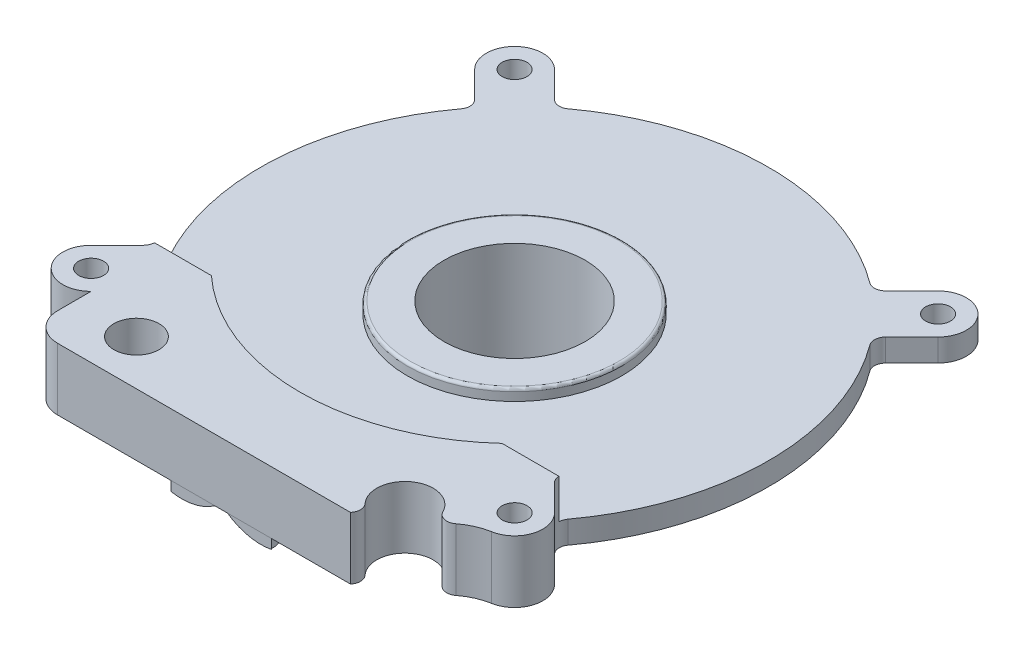
SolidWorks part; units mm, degrees
ref_plane "前视基准面" through (0, 0, 0) normal (0, 0, 1) x (1, 0, 0)
ref_plane "上视基准面" through (0, 0, 0) normal (0, 1, 0) x (1, 0, 0)
ref_plane "右视基准面" through (0, 0, 0) normal (1, 0, 0) x (0, 0, -1)
sketch "草图1" plane through (0, 0, 0) normal (0, 1, 0) x (1, 0, 0)
  circle A0 centre (0, 0) radius 12.5
  circle A1 centre (0, 0) radius 15
  dimension "D1" = 30
  dimension "D2" = 25
extrude "凸台-拉伸1" add sketch "草图1" along normal blind 20
sketch "草图2" plane through (0, 20, 0) normal (0, 1, 0) x (1, 0, 0)
  circle A0 centre (0, 0) radius 17
  circle A1 centre (0, 0) radius 12.5
  dimension "D1" = 34
  dimension "D2" = 25
extrude "凸台-拉伸2" add sketch "草图2" along normal blind 6
sketch "草图3" plane through (0, 0, 0) normal (0, -1, 0) x (1, 0, 0)
  line L0 (0, 0) -> (9.5, 0) construction
  circle A0 centre (0, 0) radius 7
  circle A2 centre (0, 0) radius 12.5
  circle A3 centre (9.5, 0) radius 1.65
  circle A4 centre (-4.75, -8.2272) radius 1.65
  circle A5 centre (-4.75, 8.2272) radius 1.65
  point P12 (0, 0)
  dimension "D1" = 14
  dimension "D2" = 25
  dimension "D3" = 3.3
  dimension "D4" = 9.5
  dimension "D5" = 3
extrude "凸台-拉伸3" add sketch "草图3" against normal blind 3
sketch "草图5" plane through (0, 26, 0) normal (0, 1, 0) x (1, 0, 0)
  line L1 (19, 19) -> (-19, 19)
  line L2 (19, 19) -> (19, -19)
  line L3 (19, -19) -> (-19, -19)
  line L4 (-19, 19) -> (-19, -19)
  line L5 (19, 19) -> (-19, -19) construction
  line L6 (19, -19) -> (-19, 19) construction
  circle A0 centre (0, 0) radius 19
  circle A1 centre (0, 0) radius 17
  point P0 (0, 0)
  circle M3 centre (0, 0) radius 17
  dimension "D3" = 34
  dimension "D1" = 38
  dimension "D2" = 38
extrude "凸台-拉伸5" add sketch "草图5" against normal blind 2 contours A0 M3
sketch "草图6" plane through (0, 26, 0) normal (0, 1, 0) x (1, 0, 0)
  line L1 (13, -13) -> (-13, -13)
  line L2 (13, -13) -> (13, 13)
  line L3 (13, 13) -> (-13, 13)
  line L4 (-13, -13) -> (-13, 13)
  line L5 (13, -13) -> (-13, 13) construction
  line L6 (13, 13) -> (-13, -13) construction
  circle A1 centre (0, 0) radius 12.5
  point P0 (0, 0)
  dimension "D2" = 25
  dimension "D1" = 90
  dimension "D3" = 26
extrude "凸台-拉伸6" add sketch "草图6" along normal blind 2
sketch "草图7" plane through (0, 24, 0) normal (0, -1, 0) x (1, 0, 0)
  circle A0 centre (0, 0) radius 17
  circle A1 centre (0, 0) radius 45
  dimension "D1" = 90
extrude "凸台-拉伸7" add sketch "草图7" along normal blind 4
sketch "草图8" plane through (0, 24, 0) normal (0, 1, 0) x (1, 0, 0)
  line L0 (-41.0355, -33.9645) -> (-35.1583, -28.0872)
  line L1 (-37.5, -37.5) -> (37.5, -37.5) construction
  line L2 (-37.5, -37.5) -> (-37.5, 37.5) construction
  line L3 (-37.5, 37.5) -> (37.5, 37.5) construction
  line L4 (37.5, -37.5) -> (37.5, 37.5) construction
  line L5 (-37.5, -37.5) -> (37.5, 37.5) construction
  line L6 (-37.5, 37.5) -> (37.5, -37.5) construction
  line L7 (-33.9645, -41.0355) -> (-28.0872, -35.1583)
  line L8 (-41.0355, 33.9645) -> (-35.1583, 28.0872)
  line L9 (-33.9645, 41.0355) -> (-28.0872, 35.1583)
  line L12 (28.0872, 35.1583) -> (33.9645, 41.0355)
  line L13 (35.1583, 28.0872) -> (41.0355, 33.9645)
  line L14 (35.1583, -28.0872) -> (41.0355, -33.9645)
  line L15 (28.0872, -35.1583) -> (33.9645, -41.0355)
  circle A0 centre (-37.5, 37.5) radius 2.2
  circle A1 centre (-37.5, -37.5) radius 2.2
  circle A2 centre (37.5, -37.5) radius 2.2
  circle A3 centre (37.5, 37.5) radius 2.2
  arc A4 (-33.9645, 41.0355) -> (-41.0355, 33.9645) centre (-37.5, 37.5) ccw
  arc A5 (-41.0355, -33.9645) -> (-33.9645, -41.0355) centre (-37.5, -37.5) ccw
  arc A6 (33.9645, -41.0355) -> (41.0355, -33.9645) centre (37.5, -37.5) ccw
  arc A7 (41.0355, 33.9645) -> (33.9645, 41.0355) centre (37.5, 37.5) ccw
  arc A8 (-28.0872, 35.1583) -> (-35.1583, 28.0872) centre (0, 0) ccw
  arc A9 (-35.1583, -28.0872) -> (-28.0872, -35.1583) centre (0, 0) ccw
  arc A10 (35.1583, 28.0872) -> (28.0872, 35.1583) centre (0, 0) ccw
  arc A11 (28.0872, -35.1583) -> (35.1583, -28.0872) centre (0, 0) ccw
  point P0 (0, 0)
  dimension "D3" = 4.4
  dimension "D4" = 10
  dimension "D5" = 45
  dimension "D1" = 75
  dimension "D2" = 75
extrude "凸台-拉伸8" add sketch "草图8" against normal up to surface (4 mm away) up to face at (0, 20, 15)
sketch "草图9" plane through (0, 24, 0) normal (0, 1, 0) x (1, 0, 0)
  line L0 (28.0872, -35.1583) -> (33.9645, -41.0355) construction
  line L1 (28.0872, -35.1583) -> (33.9645, -41.0355)
  line L2 (22.9064, -51.9624) -> (27.6497, -50.7984) construction
  line L3 (22.9064, -51.9624) -> (27.6497, -50.7984)
  line L4 (-33.9645, -41.0355) -> (-28.0872, -35.1583) construction
  line L5 (-33.9645, -41.0355) -> (-28.0872, -35.1583)
  line L6 (22.9064, -51.9624) -> (-33.9645, -51.9624)
  line L7 (-33.9645, -51.9624) -> (-33.9645, -41.0355)
  circle A1 centre (-23.0016, -43.9607) radius 4
  arc A2 (31.0086, -48.1213) -> (27.6497, -50.7984) centre (26.5148, -45.9289) ccw
  arc A4 (38.3693, -42.4239) -> (31.0459, -48.0431) centre (40.1079, -52.2716) ccw
  arc A5 (-28.0872, -35.1583) -> (28.0872, -35.1583) centre (0, 0) ccw construction
  arc A6 (-28.0872, -35.1583) -> (28.0872, -35.1583) centre (0, 0) ccw
  arc A10 (33.9645, -41.0355) -> (41.0355, -33.9645) centre (37.5, -37.5) ccw construction
  arc A11 (33.9645, -41.0355) -> (38.3693, -42.4239) centre (37.5, -37.5) ccw
  line M6 (-33.9645, -41.0355) -> (-28.0872, -35.1583)
  arc M7 (-28.0872, -35.1583) -> (28.0872, -35.1583) centre (0, 0) ccw
  line M8 (28.0872, -35.1583) -> (33.9645, -41.0355)
  arc M9 (33.9645, -41.0355) -> (41.0355, -33.9645) centre (37.5, -37.5) ccw
  dimension "D1" = 20
  dimension "D2" = 8
extrude "凸台-拉伸9" add sketch "草图9" against normal up to surface (4 mm away) contours A4 L7 L6 L3 A2 A1 M9 M8 M7 M6 up to face at (0, 20, 15)
fillet "圆角1" radius 2 2 edges at (31.0459, 22, 48.0431) (27.6497, 22, 50.7984)
sketch "草图10" plane through (0, 26, 0) normal (0, 1, 0) x (1, 0, 0)
  circle A0 centre (0, 0) radius 19
extrude "切除-拉伸1" cut sketch "草图10" along normal through all
fillet "圆角2" radius 0.5 1 edges at (0, 26, 19)
fillet "圆角3" radius 5 1 edges at (-33.9645, 22, 51.9624)
sketch "草图11" plane through (0, 0, 0) normal (0, -1, 0) x (1, 0, 0)
  circle A0 centre (-4.75, 8.2272) radius 3
  circle A1 centre (9.5, 0) radius 3
  circle A2 centre (-4.75, -8.2272) radius 3
  dimension "D1" = 6
extrude "切除-拉伸2" cut sketch "草图11" against normal blind 1.5
sketch "草图12" plane through (0, 20, 0) normal (0, -1, 0) x (1, 0, 0)
  circle A0 centre (0, 0) radius 15
  circle A1 centre (0, 0) radius 15.75
  dimension "D1" = 30
  dimension "D2" = 31.5
extrude "凸台-拉伸10" add sketch "草图12" along normal blind 1
sketch "草图13" plane through (0, 24, 0) normal (0, 1, 0) x (1, 0, 0)
  line L0 (-35.2577, -27.9624) -> (35.2577, -27.9624)
  line L8 (-33.9645, -41.0355) -> (-33.9645, -46.9624)
  line L9 (-28.9645, -51.9624) -> (22.9064, -51.9624)
  line L10 (41.0355, -33.9645) -> (35.1583, -28.0872)
  line L11 (35.1583, 28.0872) -> (41.0355, 33.9645)
  line L12 (33.9645, 41.0355) -> (28.0872, 35.1583)
  line L13 (-28.0872, 35.1583) -> (-33.9645, 41.0355)
  line L14 (-41.0355, 33.9645) -> (-35.1583, 28.0872)
  line L15 (-35.1583, -28.0872) -> (-41.0355, -33.9645)
  line L16 (-33.9645, -41.0355) -> (-33.9645, -46.9624)
  line L17 (-28.9645, -51.9624) -> (22.9064, -51.9624)
  line L18 (41.0355, -33.9645) -> (35.1583, -28.0872)
  line L23 (-35.1583, -28.0872) -> (-41.0355, -33.9645)
  arc A0 (-35.2577, -27.9624) -> (35.2577, -27.9624) centre (0, 0) ccw
  arc A3 (-25.7314, -27.9624) -> (25.7314, -27.9624) centre (0, 0) ccw
  arc A4 (35.1583, 28.0872) -> (28.0872, 35.1583) centre (0, 0) ccw
  arc A12 (-33.9645, -46.9624) -> (-28.9645, -51.9624) centre (-28.9645, -46.9624) ccw
  arc A13 (22.9064, -51.9624) -> (22.8419, -49.3216) centre (21.3728, -50.6786) ccw
  arc A14 (30.9802, -43.6793) -> (22.8419, -49.3216) centre (26.5148, -45.9289) ccw
  arc A15 (30.9802, -43.6793) -> (33.9899, -44.3614) centre (32.7663, -42.7794) ccw
  arc A16 (38.3693, -42.4239) -> (33.9899, -44.3614) centre (40.1079, -52.2716) ccw
  arc A17 (38.3693, -42.4239) -> (41.0355, -33.9645) centre (37.5, -37.5) ccw
  arc A18 (35.1583, -28.0872) -> (35.1583, 28.0872) centre (0, 0) ccw
  arc A19 (41.0355, 33.9645) -> (33.9645, 41.0355) centre (37.5, 37.5) ccw
  arc A20 (28.0872, 35.1583) -> (-28.0872, 35.1583) centre (0, 0) ccw
  arc A21 (-33.9645, 41.0355) -> (-41.0355, 33.9645) centre (-37.5, 37.5) ccw
  arc A22 (-35.1583, 28.0872) -> (-35.1583, -28.0872) centre (0, 0) ccw
  arc A23 (-41.0355, -33.9645) -> (-33.9645, -41.0355) centre (-37.5, -37.5) ccw
  arc A24 (-33.9645, -46.9624) -> (-28.9645, -51.9624) centre (-28.9645, -46.9624) ccw
  arc A25 (22.9064, -51.9624) -> (22.8419, -49.3216) centre (21.3728, -50.6786) ccw
  arc A26 (30.9802, -43.6793) -> (22.8419, -49.3216) centre (26.5148, -45.9289) ccw
  arc A27 (30.9802, -43.6793) -> (33.9899, -44.3614) centre (32.7663, -42.7794) ccw
  arc A28 (38.3693, -42.4239) -> (33.9899, -44.3614) centre (40.1079, -52.2716) ccw
  arc A29 (38.3693, -42.4239) -> (41.0355, -33.9645) centre (37.5, -37.5) ccw
  arc A30 (35.1583, -28.0872) -> (35.2577, -27.9624) centre (0, 0) ccw
  arc A34 (-35.2577, -27.9624) -> (-35.1583, -28.0872) centre (0, 0) ccw
  arc A35 (-41.0355, -33.9645) -> (-33.9645, -41.0355) centre (-37.5, -37.5) ccw
  line M22 (-33.9645, -41.0355) -> (-33.9645, -46.9624)
  arc M23 (-33.9645, -46.9624) -> (-28.9645, -51.9624) centre (-28.9645, -46.9624) ccw
  line M24 (-28.9645, -51.9624) -> (22.9064, -51.9624)
  arc M25 (22.9064, -51.9624) -> (22.8419, -49.3216) centre (21.3728, -50.6786) ccw
  arc M26 (22.8419, -49.3216) -> (30.9802, -43.6793) centre (26.5148, -45.9289) cw
  arc M27 (30.9802, -43.6793) -> (33.9899, -44.3614) centre (32.7663, -42.7794) ccw
  arc M28 (33.9899, -44.3614) -> (38.3693, -42.4239) centre (40.1079, -52.2716) cw
  arc M29 (38.3693, -42.4239) -> (41.0355, -33.9645) centre (37.5, -37.5) ccw
  line M30 (41.0355, -33.9645) -> (35.1583, -28.0872)
  arc M31 (35.1583, -28.0872) -> (35.1583, 28.0872) centre (0, 0) ccw
  arc M39 (-35.1583, 28.0872) -> (-35.1583, -28.0872) centre (0, 0) ccw
  line M40 (-35.1583, -28.0872) -> (-41.0355, -33.9645)
  arc M41 (-41.0355, -33.9645) -> (-33.9645, -41.0355) centre (-37.5, -37.5) ccw
  circle M42 centre (-37.5, -37.5) radius 2.2
  circle M45 centre (37.5, -37.5) radius 2.2
  circle M46 centre (-23.0016, -43.9607) radius 4
  dimension "D2" = 76
  dimension "D3" = 24
  dimension "D1" = 0
extrude "凸台-拉伸11" add sketch "草图13" along normal blind 4.2 contours A3 L0 A0 M39 M31 | A0 M40 M41 M22 M23 M24 M25 M26 M27 M28 M29 M30 M45 M46 M42
sketch "草图14" plane through (0, 0, 51.9624) normal (0, 0, 1) x (1, 0, 0)
  line L0 (-8.9, 11.1) -> (-8.9, 20)
  line L1 (8.9, 11.1) -> (8.9, 20)
  line L4 (22.9064, 20) -> (22.9064, 28.2)
  line L5 (22.9064, 28.2) -> (-28.9645, 28.2)
  line L6 (-28.9645, 28.2) -> (-28.9645, 20)
  line L7 (-28.9645, 20) -> (22.9064, 20)
  line L8 (22.9064, 20) -> (22.9064, 28.2)
  line L9 (22.9064, 28.2) -> (-28.9645, 28.2)
  line L10 (-28.9645, 28.2) -> (-28.9645, 20)
  line L11 (-28.9645, 20) -> (22.9064, 20)
  circle A0 centre (0, 11.1) radius 8.9
  circle A1 centre (-7, 28.3) radius 10.1699
  circle A2 centre (7, 28.3) radius 10.1699
  circle A3 centre (0, 11.1) radius 8.4 construction
  line M8 (-28.9645, 20) -> (22.9064, 20)
  dimension "D2" = 17.8
  dimension "D3" = 7
  dimension "D6" = 16.8
  dimension "D4" = 7
  dimension "D5" = 17.2
  dimension "D1" = 0
extrude "凸台-拉伸12" add sketch "草图14" against normal blind 7 separate body contours L0 A1 A0 M8 | A0 A1 | A2 A0 L1 M8 | A0 A2
chamfer "倒角1" distance 1.9 angle 73 1 edges at (4.8394, 18.3623, 44.9624)
chamfer "倒角2" distance 1.9 angle 73 1 edges at (-4.8394, 18.3623, 44.9624)
sketch "草图15" plane through (0, 20, 0) normal (0, -1, 0) x (1, 0, 0)
  line L0 (8.75, 51.9615) -> (12.7263, 51.9624)
  line L1 (-28.9645, 51.9624) -> (22.9064, 51.9624) construction
  line L2 (12.7263, 51.9624) -> (6.3302, 38.4828)
  circle A0 centre (-30, 51.9615) radius 38.75
  dimension "D1" = 77.5
extrude "切除-拉伸4" cut sketch "草图15" along normal blind 10 contours A0 L2 L0
fillet "圆角4" radius 2 10 edges at (-35.2577, 26.1, 27.9624) (35.2577, 26.1, 27.9624) (-35.2081, 28.2, 28.0248) (35.2081, 28.2, 28.0248) (-35.1583, 24.1, 28.0872) (28.0872, 22, -35.1583) (35.1583, 22, -28.0872) (-35.1583, 22, -28.0872) (-28.0872, 22, -35.1583) (35.1583, 24.1, 28.0872)
sketch "草图16" plane through (0, 28.2, 0) normal (0, 1, 0) x (1, 0, 0)
  line L6 (-25.7314, -27.9624) -> (-35.8137, -27.9624)
  line L7 (-36.3989, -29.3278) -> (-41.0355, -33.9645)
  line L8 (-33.9645, -41.0355) -> (-33.9645, -46.9624)
  line L9 (-28.9645, -51.9624) -> (22.9064, -51.9624)
  line L10 (41.0355, -33.9645) -> (36.3989, -29.3278)
  line L11 (35.8137, -27.9624) -> (25.7314, -27.9624)
  line L12 (-25.7314, -27.9624) -> (-35.8137, -27.9624)
  line L13 (-36.3989, -29.3278) -> (-41.0355, -33.9645)
  line L14 (-33.9645, -41.0355) -> (-33.9645, -46.9624)
  line L15 (-28.9645, -51.9624) -> (22.9064, -51.9624)
  line L16 (41.0355, -33.9645) -> (36.3989, -29.3278)
  line L17 (35.8137, -27.9624) -> (25.7314, -27.9624)
  circle A0 centre (-37.5, -37.5) radius 2.2
  circle A1 centre (-23.0016, -43.9607) radius 4
  circle A2 centre (37.5, -37.5) radius 2.2
  arc A10 (-25.7314, -27.9624) -> (25.7314, -27.9624) centre (0, 0) ccw
  arc A11 (-36.3989, -29.3278) -> (-35.8137, -27.9624) centre (-37.8131, -27.9136) ccw
  arc A12 (-41.0355, -33.9645) -> (-33.9645, -41.0355) centre (-37.5, -37.5) ccw
  arc A13 (-33.9645, -46.9624) -> (-28.9645, -51.9624) centre (-28.9645, -46.9624) ccw
  arc A14 (22.9064, -51.9624) -> (22.8419, -49.3216) centre (21.3728, -50.6786) ccw
  arc A15 (30.9802, -43.6793) -> (22.8419, -49.3216) centre (26.5148, -45.9289) ccw
  arc A16 (30.9802, -43.6793) -> (33.9899, -44.3614) centre (32.7663, -42.7794) ccw
  arc A17 (38.3693, -42.4239) -> (33.9899, -44.3614) centre (40.1079, -52.2716) ccw
  arc A18 (38.3693, -42.4239) -> (41.0355, -33.9645) centre (37.5, -37.5) ccw
  arc A19 (35.8137, -27.9624) -> (36.3989, -29.3278) centre (37.8131, -27.9136) ccw
  arc A20 (-25.7314, -27.9624) -> (25.7314, -27.9624) centre (0, 0) ccw
  arc A21 (-36.3989, -29.3278) -> (-35.8137, -27.9624) centre (-37.8131, -27.9136) ccw
  arc A22 (-41.0355, -33.9645) -> (-33.9645, -41.0355) centre (-37.5, -37.5) ccw
  arc A23 (-33.9645, -46.9624) -> (-28.9645, -51.9624) centre (-28.9645, -46.9624) ccw
  arc A24 (22.9064, -51.9624) -> (22.8419, -49.3216) centre (21.3728, -50.6786) ccw
  arc A25 (30.9802, -43.6793) -> (22.8419, -49.3216) centre (26.5148, -45.9289) ccw
  arc A26 (30.9802, -43.6793) -> (33.9899, -44.3614) centre (32.7663, -42.7794) ccw
  arc A27 (38.3693, -42.4239) -> (33.9899, -44.3614) centre (40.1079, -52.2716) ccw
  arc A28 (38.3693, -42.4239) -> (41.0355, -33.9645) centre (37.5, -37.5) ccw
  arc A29 (35.8137, -27.9624) -> (36.3989, -29.3278) centre (37.8131, -27.9136) ccw
  dimension "D1" = 0
extrude "凸台-拉伸13" add sketch "草图16" along normal blind 3
sketch "草图17" plane through (0, 31.2, 0) normal (0, 1, 0) x (1, 0, 0)
  line L6 (-25.7314, -27.9624) -> (-35.8137, -27.9624)
  line L7 (-36.3989, -29.3278) -> (-41.0355, -33.9645)
  line L8 (-33.9645, -41.0355) -> (-33.9645, -46.9624)
  line L9 (-28.9645, -51.9624) -> (22.9064, -51.9624)
  line L10 (41.0355, -33.9645) -> (36.3989, -29.3278)
  line L11 (35.8137, -27.9624) -> (25.7314, -27.9624)
  line L12 (-25.7314, -27.9624) -> (-35.8137, -27.9624)
  line L13 (-36.3989, -29.3278) -> (-41.0355, -33.9645)
  line L14 (-33.9645, -41.0355) -> (-33.9645, -46.9624)
  line L15 (-28.9645, -51.9624) -> (22.9064, -51.9624)
  line L16 (41.0355, -33.9645) -> (36.3989, -29.3278)
  line L17 (35.8137, -27.9624) -> (25.7314, -27.9624)
  arc A10 (-25.7314, -27.9624) -> (25.7314, -27.9624) centre (0, 0) ccw
  arc A11 (-36.3989, -29.3278) -> (-35.8137, -27.9624) centre (-37.8131, -27.9136) ccw
  arc A12 (-41.0355, -33.9645) -> (-33.9645, -41.0355) centre (-37.5, -37.5) ccw
  arc A13 (-33.9645, -46.9624) -> (-28.9645, -51.9624) centre (-28.9645, -46.9624) ccw
  arc A14 (22.9064, -51.9624) -> (22.8419, -49.3216) centre (21.3728, -50.6786) ccw
  arc A15 (30.9802, -43.6793) -> (22.8419, -49.3216) centre (26.5148, -45.9289) ccw
  arc A16 (30.9802, -43.6793) -> (33.9899, -44.3614) centre (32.7663, -42.7794) ccw
  arc A17 (38.3693, -42.4239) -> (33.9899, -44.3614) centre (40.1079, -52.2716) ccw
  arc A18 (38.3693, -42.4239) -> (41.0355, -33.9645) centre (37.5, -37.5) ccw
  arc A19 (35.8137, -27.9624) -> (36.3989, -29.3278) centre (37.8131, -27.9136) ccw
  arc A20 (-25.7314, -27.9624) -> (25.7314, -27.9624) centre (0, 0) ccw
  arc A21 (-36.3989, -29.3278) -> (-35.8137, -27.9624) centre (-37.8131, -27.9136) ccw
  arc A22 (-41.0355, -33.9645) -> (-33.9645, -41.0355) centre (-37.5, -37.5) ccw
  arc A23 (-33.9645, -46.9624) -> (-28.9645, -51.9624) centre (-28.9645, -46.9624) ccw
  arc A24 (22.9064, -51.9624) -> (22.8419, -49.3216) centre (21.3728, -50.6786) ccw
  arc A25 (30.9802, -43.6793) -> (22.8419, -49.3216) centre (26.5148, -45.9289) ccw
  arc A26 (30.9802, -43.6793) -> (33.9899, -44.3614) centre (32.7663, -42.7794) ccw
  arc A27 (38.3693, -42.4239) -> (33.9899, -44.3614) centre (40.1079, -52.2716) ccw
  arc A28 (38.3693, -42.4239) -> (41.0355, -33.9645) centre (37.5, -37.5) ccw
  arc A29 (35.8137, -27.9624) -> (36.3989, -29.3278) centre (37.8131, -27.9136) ccw
  dimension "D1" = 0
extrude "切除-拉伸5" cut sketch "草图17" against normal blind 0.2
